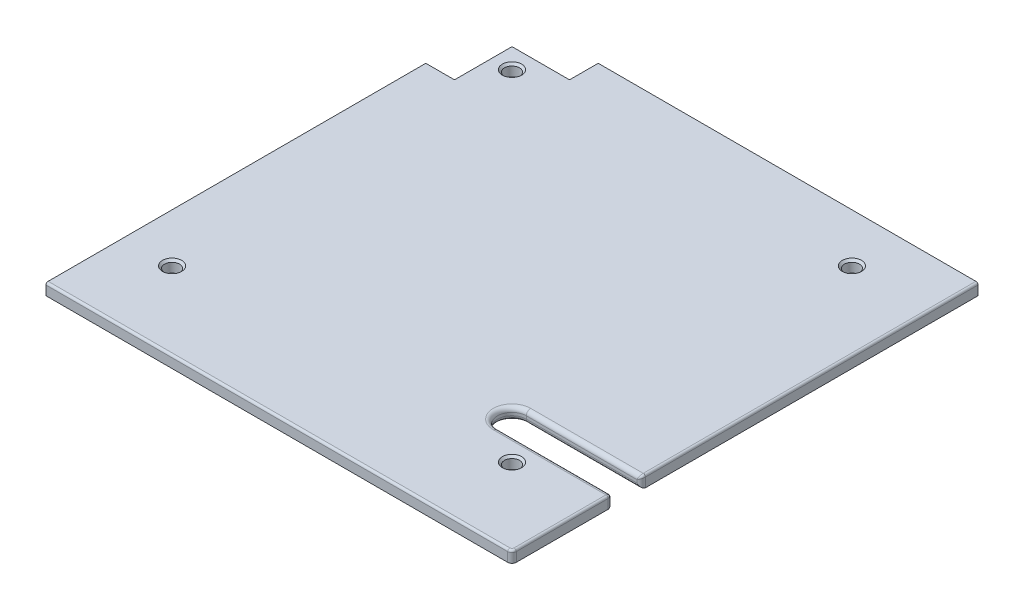
SolidWorks part; units mm, degrees
ref_plane "Front Plane" through (0, 0, 0) normal (0, 0, 1) x (1, 0, 0)
ref_plane "Top Plane" through (0, 0, 0) normal (0, 1, 0) x (1, 0, 0)
ref_plane "Right Plane" through (0, 0, 0) normal (1, 0, 0) x (0, 0, -1)
sketch "Sketch1" plane through (0, 0, 0) normal (0, 1, 0) x (1, 0, 0)
  line L0 (0, -76.2) -> (0, 76.2) construction
  line L1 (-66.25, -66.25) -> (66.25, -66.25) construction
  line L2 (-66.25, -66.25) -> (-66.25, 66.25) construction
  line L3 (-66.25, 66.25) -> (66.25, 66.25) construction
  line L4 (66.25, -66.25) -> (66.25, 66.25) construction
  line L5 (-66.25, -66.25) -> (66.25, 66.25) construction
  line L6 (-66.25, 66.25) -> (66.25, -66.25) construction
  line L11 (-66.2, 46.15) -> (-76.2, 46.15)
  line L12 (-46.15, 66.2) -> (-46.15, 76.2)
  line L15 (-46.15, 76.2) -> (86.25, 76.2)
  line L16 (86.25, 76.2) -> (86.25, -41.25)
  line L17 (84.75, -86.25) -> (-76.2, -86.25)
  line L18 (-76.2, -86.25) -> (-76.2, 46.15)
  line L19 (-66.2, 46.15) -> (-66.2, 66.2)
  line L20 (-66.2, 66.2) -> (-46.15, 66.2)
  line L21 (46.25, -51.25) -> (86.25, -51.25)
  line L22 (46.25, -41.25) -> (86.25, -41.25)
  line L23 (86.25, -51.25) -> (86.25, -84.75)
  circle A0 centre (-59.25, 59.25) radius 1.85
  circle A1 centre (-59.25, -59.25) radius 1.85
  circle A3 centre (59.25, -59.25) radius 1.85
  circle A4 centre (59.25, 59.25) radius 1.85
  circle A5 centre (-59.25, 59.25) radius 2.6
  circle A6 centre (59.25, 59.25) radius 2.6
  circle A7 centre (59.25, -59.25) radius 2.6
  circle A8 centre (-59.25, -59.25) radius 2.6
  arc A9 (86.25, -84.75) -> (84.75, -86.25) centre (84.75, -84.75) cw
  arc A11 (46.25, -41.25) -> (46.25, -51.25) centre (46.25, -46.25) ccw
  point P0 (0, 0)
  point P16 (0, 0)
  dimension "D2" = 3.7
  dimension "D3" = 7
  dimension "D7" = 20
  dimension "D9" = 5.2
  dimension "D10" = 1.5
  dimension "D12" = 10
  dimension "D13" = 20
  dimension "D14" = 35
  dimension "D1" = 132.5
  dimension "D4" = 9.95
  dimension "D5" = 20
  dimension "D6" = 20.1
  dimension "D8" = 9.95
  dimension "D11" = 10
extrude "Boss-Extrude1" add sketch "Sketch1" along normal mid plane 4 contours L18 L17 L16 L15 L12 L11 A8 A7 A6 A5 | A5 A0 | A6 A4 | A7 A3 | A8 A1 region at (5.4011, 0, 5.7132) region at (-61.7765, 0, -59.25) region at (56.7235, 0, -59.25) region at (56.7235, 0, 59.25) region at (-61.7765, 0, 59.25)
chamfer "Chamfer2" distance 1.5 angle 45 4 edges at (-59.25, 2, -57.4) (59.25, 2, -57.4) (-59.25, 2, 61.1) (59.25, 2, 61.1)
extrude "Cut-Extrude2" cut sketch "Sketch1<4>" along normal up to surface (2 mm away) from surface contours A5 A0 | A8 A1 | A7 A3 | A6 A4 region at (-61.7765, 0, -59.25) region at (56.7235, 0, -59.25) region at (56.7235, 0, 59.25) region at (-61.7765, 0, 59.25) up to face at (59.25, 2, -55.9) starting at face at (10.8047, -2, 5.0354)
sketch "Sketch1<4>" plane through (0, 0, 0) normal (0, 1, 0) x (1, 0, 0) same geometry as "Sketch1"
fillet "Fillet1" radius 0.75 4 edges at (86.25, 2, -17.475) (85.8107, 2, 85.8107) (4.275, 2, 86.25) (86.25, 2, 68)
fillet "Fillet2" radius 1.5 10 edges at (66.25, -2, 41.25) (41.25, -2, 46.25) (65.875, 2, 41.25) (86.25, -0.375, 51.25) (86.0303, 1.7803, 51.25) (65.875, 2, 51.25) (66.25, -2, 51.25) (86.25, -0.375, 41.25) (41.25, 2, 46.25) (86.0303, 1.7803, 41.25)
